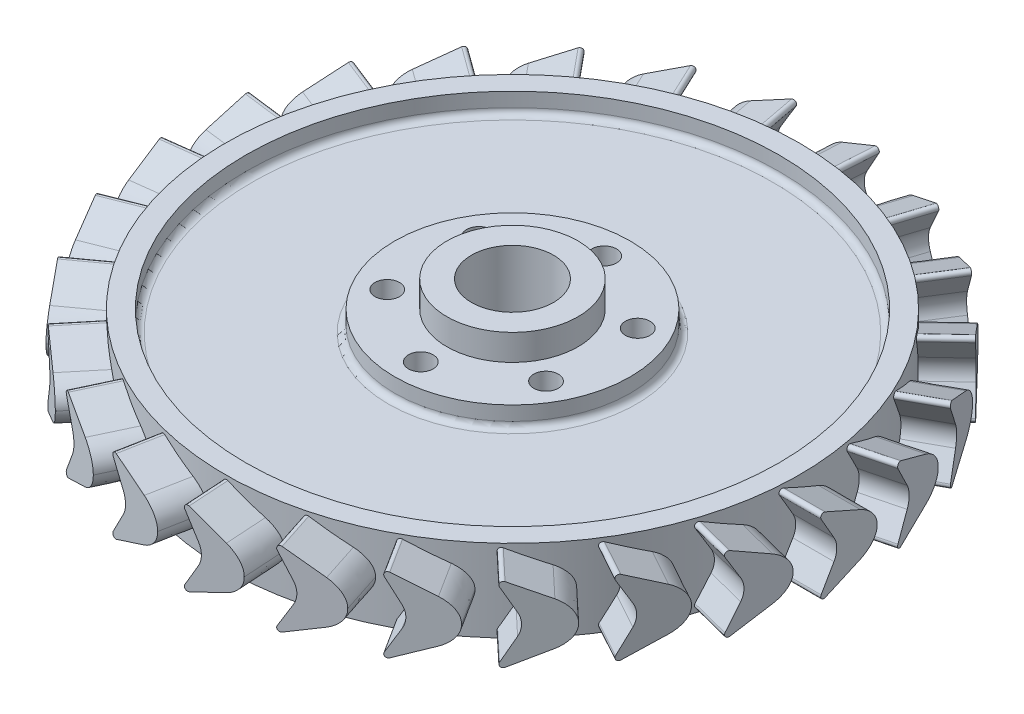
SolidWorks part; units mm, degrees
ref_plane "Front Plane" through (0, 0, 0) normal (0, 0, 1) x (1, 0, 0)
ref_plane "Top Plane" through (0, 0, 0) normal (0, 1, 0) x (1, 0, 0)
ref_plane "Right Plane" through (0, 0, 0) normal (1, 0, 0) x (0, 0, -1)
sketch "Sketch1" plane through (0, 0, 0) normal (0, 0, 1) x (1, 0, 0)
  line L0 (0, 0) -> (0, 10)
  line L3 (32.5, 7.5) -> (32.5, 10)
  line L4 (32.5, 10) -> (35, 10)
  line L5 (35, 10) -> (35, 0)
  line L6 (35, 0) -> (32.5, 0)
  line L7 (32.5, 0) -> (32.5, 2.5)
  line L9 (14.35, 0) -> (0, 0)
  line L10 (0, 5) -> (35, 5) construction
  line L11 (32.5, 7.5) -> (14.35, 7.5)
  line L12 (14.35, 7.5) -> (14.35, 10)
  line L13 (14.35, 0) -> (14.35, 2.5)
  line L14 (14.35, 2.5) -> (32.5, 2.5)
  line L15 (14.35, 10) -> (8, 10)
  line L16 (8, 10) -> (8, 13.175)
  line L17 (8, 13.175) -> (0, 13.175)
  line L18 (0, 13.175) -> (0, 10)
  dimension "D1" = 35
  dimension "D2" = 10
  dimension "D3" = 2.5
  dimension "D4" = 5
  dimension "D6" = 14.35
  dimension "D5" = 10
  dimension "D7" = 3.175
  dimension "D8" = 8
revolve "Main Body" add sketch "Sketch1" angle 360 about L0
fillet "Hub Fillets" radius 0.762 4 edges at (0, 7.5, -14.35) (0, 7.5, -32.5) (0, 2.5, -14.35) (0, 2.5, -32.5)
ref_plane "Blade Drawing Plane" through (35, 0, 0) normal (1, 0, 0) x (0, 0, -1)
sketch "Sketch3" plane through (0, 0, 0) normal (0, -1, 0) x (-1, 0, 0)
  point P0 (0, 11.175)
  dimension "D1" = 11.175
hole_wizard "Ø4.0mm Dowel Hole1" positions "Sketch3" profile "Sketch4" hole size "Ø4.0" standard "ANSI Metric" end condition through all
sketch "Sketch4" plane through (0, 0, -11.175) normal (1, 0, 0) x (0, 0, -1)
  line L0 (0, 0) -> (0, 13.175)
  line L1 (0, 13.175) -> (1.5, 13.175)
  line L2 (1.5, 13.175) -> (1.5, 0)
  line L5 (1.5, 0) -> (0, 0)
  line L11 (0, -6.35) -> (0, 107.95) construction
  dimension "Thru Hole Dia." = 3
  dimension "Thru Hole Depth" = 13.175
pattern_circular "CirPattern1" count 6 over 360 about axis through (0, 0, 0) along (0, -1, 0) of "Ø4.0mm Dowel Hole1"
sketch "Sketch5" plane through (0, 13.175, 0) normal (0, 1, 0) x (1, 0, 0)
  point P0 (0, 0)
hole_wizard "Ø10.0mm Dowel Hole1" positions "Sketch5" profile "Sketch6" hole size "Ø10.0" standard "ANSI Metric" end condition through all
sketch "Sketch6" plane through (0, 13.175, 0) normal (1, 0, 0) x (0, 0, 1)
  line L0 (0, 0) -> (0, 13.175)
  line L1 (0, 13.175) -> (5, 13.175)
  line L2 (5, 13.175) -> (5, 0)
  line L5 (5, 0) -> (0, 0)
  line L11 (0, -6.35) -> (0, 107.95) construction
  dimension "Thru Hole Dia." = 10
  dimension "Thru Hole Depth" = 13.175
sketch "Sketch11" plane through (35, 0, 0) normal (1, 0, 0) x (0, 0, -1)
  line L0 (0, 630) -> (840, 630)
  line L1 (840, 630) -> (840, 0)
  line L2 (840, 0) -> (0, 0)
  line L3 (0, 0) -> (0, 630)
  line L4 (0, 630) -> (840, 630)
  line L5 (840, 630) -> (840, 0)
  line L6 (840, 0) -> (0, 0)
  line L7 (0, 0) -> (0, 630)
  line L8 (618.7249, 408.0901) -> (620.1519, 404.8008)
  line L9 (620.1519, 404.8008) -> (621.579, 401.5114)
  line L10 (621.579, 401.5114) -> (623.006, 398.2221)
  line L11 (623.006, 398.2221) -> (624.433, 394.9328)
  line L12 (624.433, 394.9328) -> (625.86, 391.6435)
  line L13 (625.86, 391.6435) -> (627.287, 388.3542)
  line L14 (627.287, 388.3542) -> (628.7141, 385.0649)
  line L15 (628.7141, 385.0649) -> (630.1411, 381.7756)
  line L16 (630.1411, 381.7756) -> (631.5681, 378.4863)
  line L17 (631.5681, 378.4863) -> (632.9951, 375.197)
  line L18 (632.9951, 375.197) -> (634.4221, 371.9077)
  line L19 (634.4221, 371.9077) -> (635.8492, 368.6183)
  line L20 (635.8492, 368.6183) -> (637.2762, 365.329)
  line L21 (637.2762, 365.329) -> (638.7032, 362.0397)
  line L22 (638.7032, 362.0397) -> (640.1302, 358.7504)
  line L23 (640.1302, 358.7504) -> (641.5573, 355.4611)
  line L24 (641.5573, 355.4611) -> (642.9843, 352.1718)
  line L25 (642.9843, 352.1718) -> (644.4113, 348.8825)
  line L26 (644.4113, 348.8825) -> (645.8383, 345.5932)
  line L27 (645.8383, 345.5932) -> (647.2653, 342.3039)
  line L28 (647.2653, 342.3039) -> (648.6924, 339.0146)
  line L29 (648.6924, 339.0146) -> (650.1194, 335.7252)
  line L30 (650.1194, 335.7252) -> (651.5464, 332.4359)
  line L31 (651.5464, 332.4359) -> (652.9734, 329.1466)
  line L32 (652.9734, 329.1466) -> (654.4005, 325.8573)
  line L33 (654.4005, 325.8573) -> (655.8275, 322.568)
  line L34 (655.8275, 322.568) -> (657.2545, 319.2787)
  line L35 (657.2545, 319.2787) -> (658.6815, 315.9894)
  line L36 (658.6815, 315.9894) -> (660.1085, 312.7001)
  line L37 (660.1085, 312.7001) -> (661.5355, 309.4107)
  line L38 (661.5355, 309.4107) -> (662.9626, 306.1214)
  line L39 (662.9626, 306.1214) -> (664.3896, 302.8321)
  line L40 (664.3896, 302.8321) -> (665.8167, 299.5428)
  line L41 (665.8167, 299.5428) -> (667.2437, 296.2535)
  line L42 (667.2437, 296.2535) -> (668.6707, 292.9642)
  line L43 (668.6707, 292.9642) -> (670.0977, 289.6749)
  line L44 (670.0977, 289.6749) -> (671.5247, 286.3856)
  line L45 (671.5247, 286.3856) -> (672.9517, 283.0963)
  line L46 (672.9517, 283.0963) -> (674.3787, 279.8069)
  line L47 (674.3787, 279.8069) -> (675.8057, 276.5176)
  line L48 (675.8057, 276.5176) -> (677.2328, 273.2283)
  line L49 (677.2328, 273.2283) -> (678.6598, 269.939)
  line L50 (678.6598, 269.939) -> (680.0869, 266.6497)
  line L51 (680.0869, 266.6497) -> (681.5139, 263.3604)
  line L52 (681.5139, 263.3604) -> (682.9409, 260.0711)
  line L53 (682.9409, 260.0711) -> (684.3679, 256.7818)
  line L54 (684.3679, 256.7818) -> (685.7949, 253.4925)
  line L55 (685.7949, 253.4925) -> (687.2219, 250.2032)
  line L56 (687.2219, 250.2032) -> (688.6489, 246.9138)
  line L57 (688.6489, 246.9138) -> (690.076, 243.6245)
  line L58 (690.076, 243.6245) -> (691.503, 240.3352)
  line L59 (691.503, 240.3352) -> (692.93, 237.0459)
  line L60 (692.93, 237.0459) -> (694.3571, 233.7566)
  line L61 (694.3571, 233.7566) -> (695.7841, 230.4673)
  line L62 (695.7841, 230.4673) -> (697.2111, 227.178)
  line L63 (697.2111, 227.178) -> (698.6381, 223.8887)
  line L64 (698.6381, 223.8887) -> (700.0651, 220.5993)
  line L65 (700.0651, 220.5993) -> (701.4921, 217.31)
  line L66 (701.4921, 217.31) -> (702.9191, 214.0207)
  line L67 (702.9191, 214.0207) -> (704.3462, 210.7314)
  line L68 (704.3462, 210.7314) -> (705.7732, 207.4421)
  line L69 (705.7732, 207.4421) -> (707.2002, 204.1528)
  line L70 (707.2002, 204.1528) -> (708.6273, 200.8635)
  line L71 (708.6273, 200.8635) -> (710.0543, 197.5742)
  line L72 (710.0543, 197.5742) -> (711.4813, 194.2849)
  line L73 (711.4813, 194.2849) -> (712.9083, 190.9955)
  line L74 (712.9083, 190.9955) -> (714.3353, 187.7062)
  line L75 (714.3353, 187.7062) -> (715.7623, 184.4169)
  line L76 (715.7623, 184.4169) -> (717.1893, 181.1276)
  line L77 (717.1893, 181.1276) -> (718.6164, 177.8383)
  line L78 (718.6164, 177.8383) -> (720.0434, 174.549)
  line L79 (720.0434, 174.549) -> (721.4705, 171.2597)
  line L80 (721.4705, 171.2597) -> (722.8975, 167.9704)
  line L81 (722.8975, 167.9704) -> (724.3245, 164.6811)
  line L82 (724.3245, 164.6811) -> (725.7515, 161.3918)
  line L83 (725.7515, 161.3918) -> (727.1785, 158.1024)
  line L84 (727.1785, 158.1024) -> (728.6055, 154.8131)
  line L85 (728.6055, 154.8131) -> (730.0325, 151.5238)
  line L86 (730.0325, 151.5238) -> (731.4596, 148.2345)
  line L87 (731.4596, 148.2345) -> (732.8866, 144.9452)
  line L88 (732.8866, 144.9452) -> (734.3136, 141.6559)
  line L89 (734.3136, 141.6559) -> (735.7407, 138.3666)
  line L90 (735.7407, 138.3666) -> (737.1677, 135.0773)
  line L91 (737.1677, 135.0773) -> (738.5947, 131.788)
  line L92 (738.5947, 131.788) -> (740.0217, 128.4987)
  line L93 (740.0217, 128.4987) -> (741.4487, 125.2093)
  line L94 (741.4487, 125.2093) -> (742.8757, 121.92)
  line L95 (742.8757, 121.92) -> (744.3027, 118.6307)
  line L96 (744.3027, 118.6307) -> (745.7298, 115.3414)
  line L97 (745.7298, 115.3414) -> (747.1568, 112.0521)
  line L98 (747.1568, 112.0521) -> (748.5838, 108.7628)
  line L99 (748.5838, 108.7628) -> (750.0109, 105.4734)
  line L100 (750.0109, 105.4734) -> (751.4379, 102.1841)
  line L101 (751.4379, 102.1841) -> (752.8649, 98.8948)
  line L102 (752.8649, 98.8948) -> (754.2919, 95.6055)
  line L103 (754.2919, 95.6055) -> (755.719, 92.3162)
  line L104 (755.719, 92.3162) -> (757.1459, 89.0269)
  line L105 (757.1459, 89.0269) -> (758.5729, 85.7376)
  line L106 (758.5729, 85.7376) -> (760, 82.4483)
  line L107 (109, 82.4483) -> (110.427, 85.7376)
  line L108 (110.427, 85.7376) -> (111.854, 89.0269)
  line L109 (111.854, 89.0269) -> (113.2811, 92.3162)
  line L110 (113.2811, 92.3162) -> (114.7081, 95.6055)
  line L111 (114.7081, 95.6055) -> (116.1351, 98.8948)
  line L112 (116.1351, 98.8948) -> (117.5621, 102.1841)
  line L113 (117.5621, 102.1841) -> (118.9891, 105.4734)
  line L114 (118.9891, 105.4734) -> (120.4162, 108.7628)
  line L115 (120.4162, 108.7628) -> (121.8432, 112.0521)
  line L116 (121.8432, 112.0521) -> (123.2702, 115.3414)
  line L117 (123.2702, 115.3414) -> (124.6972, 118.6307)
  line L118 (124.6972, 118.6307) -> (126.1243, 121.92)
  line L119 (126.1243, 121.92) -> (127.5513, 125.2093)
  line L120 (127.5513, 125.2093) -> (128.9783, 128.4987)
  line L121 (128.9783, 128.4987) -> (130.4053, 131.788)
  line L122 (130.4053, 131.788) -> (131.8323, 135.0773)
  line L123 (131.8323, 135.0773) -> (133.2594, 138.3666)
  line L124 (133.2594, 138.3666) -> (134.6864, 141.6559)
  line L125 (134.6864, 141.6559) -> (136.1134, 144.9452)
  line L126 (136.1134, 144.9452) -> (137.5404, 148.2345)
  line L127 (137.5404, 148.2345) -> (138.9674, 151.5238)
  line L128 (138.9674, 151.5238) -> (140.3945, 154.8131)
  line L129 (140.3945, 154.8131) -> (141.8215, 158.1024)
  line L130 (141.8215, 158.1024) -> (143.2485, 161.3918)
  line L131 (143.2485, 161.3918) -> (144.6755, 164.6811)
  line L132 (144.6755, 164.6811) -> (146.1025, 167.9704)
  line L133 (146.1025, 167.9704) -> (147.5296, 171.2597)
  line L134 (147.5296, 171.2597) -> (148.9566, 174.549)
  line L135 (148.9566, 174.549) -> (150.3836, 177.8383)
  line L136 (150.3836, 177.8383) -> (151.8106, 181.1276)
  line L137 (151.8106, 181.1276) -> (153.2376, 184.4169)
  line L138 (153.2376, 184.4169) -> (154.6647, 187.7062)
  line L139 (154.6647, 187.7062) -> (156.0917, 190.9955)
  line L140 (156.0917, 190.9955) -> (157.5187, 194.2849)
  line L141 (157.5187, 194.2849) -> (158.9457, 197.5742)
  line L142 (158.9457, 197.5742) -> (160.3728, 200.8635)
  line L143 (160.3728, 200.8635) -> (161.7998, 204.1528)
  line L144 (161.7998, 204.1528) -> (163.2268, 207.4421)
  line L145 (163.2268, 207.4421) -> (164.6538, 210.7314)
  line L146 (164.6538, 210.7314) -> (166.0808, 214.0207)
  line L147 (166.0808, 214.0207) -> (167.5079, 217.31)
  line L148 (167.5079, 217.31) -> (168.9349, 220.5993)
  line L149 (168.9349, 220.5993) -> (170.3619, 223.8887)
  line L150 (170.3619, 223.8887) -> (171.7889, 227.178)
  line L151 (171.7889, 227.178) -> (173.2159, 230.4673)
  line L152 (173.2159, 230.4673) -> (174.643, 233.7566)
  line L153 (174.643, 233.7566) -> (176.07, 237.0459)
  line L154 (176.07, 237.0459) -> (177.497, 240.3352)
  line L155 (177.497, 240.3352) -> (178.924, 243.6245)
  line L156 (178.924, 243.6245) -> (180.351, 246.9138)
  line L157 (180.351, 246.9138) -> (181.7781, 250.2032)
  line L158 (181.7781, 250.2032) -> (183.2051, 253.4925)
  line L159 (183.2051, 253.4925) -> (184.6321, 256.7818)
  line L160 (184.6321, 256.7818) -> (186.0591, 260.0711)
  line L161 (186.0591, 260.0711) -> (187.4861, 263.3604)
  line L162 (187.4861, 263.3604) -> (188.9132, 266.6497)
  line L163 (188.9132, 266.6497) -> (190.3402, 269.939)
  line L164 (190.3402, 269.939) -> (191.7672, 273.2283)
  line L165 (191.7672, 273.2283) -> (193.1942, 276.5176)
  line L166 (193.1942, 276.5176) -> (194.6213, 279.8069)
  line L167 (194.6213, 279.8069) -> (196.0483, 283.0963)
  line L168 (196.0483, 283.0963) -> (197.4753, 286.3856)
  line L169 (197.4753, 286.3856) -> (198.9023, 289.6749)
  line L170 (198.9023, 289.6749) -> (200.3293, 292.9642)
  line L171 (200.3293, 292.9642) -> (201.7564, 296.2535)
  line L172 (201.7564, 296.2535) -> (203.1834, 299.5428)
  line L173 (203.1834, 299.5428) -> (204.6104, 302.8321)
  line L174 (204.6104, 302.8321) -> (206.0374, 306.1214)
  line L175 (206.0374, 306.1214) -> (207.4644, 309.4107)
  line L176 (207.4644, 309.4107) -> (208.8915, 312.7001)
  line L177 (208.8915, 312.7001) -> (210.3185, 315.9894)
  line L178 (210.3185, 315.9894) -> (211.7455, 319.2787)
  line L179 (211.7455, 319.2787) -> (213.1725, 322.568)
  line L180 (213.1725, 322.568) -> (214.5995, 325.8573)
  line L181 (214.5995, 325.8573) -> (216.0266, 329.1466)
  line L182 (216.0266, 329.1466) -> (217.4536, 332.4359)
  line L183 (217.4536, 332.4359) -> (218.8806, 335.7252)
  line L184 (218.8806, 335.7252) -> (220.3076, 339.0146)
  line L185 (220.3076, 339.0146) -> (221.7346, 342.3039)
  line L186 (221.7346, 342.3039) -> (223.1617, 345.5932)
  line L187 (223.1617, 345.5932) -> (224.5887, 348.8825)
  line L188 (224.5887, 348.8825) -> (226.0157, 352.1718)
  line L189 (226.0157, 352.1718) -> (227.4427, 355.4611)
  line L190 (227.4427, 355.4611) -> (228.8698, 358.7504)
  line L191 (228.8698, 358.7504) -> (230.2968, 362.0397)
  line L192 (230.2968, 362.0397) -> (231.7238, 365.329)
  line L193 (231.7238, 365.329) -> (233.1508, 368.6183)
  line L194 (233.1508, 368.6183) -> (234.5778, 371.9077)
  line L195 (234.5778, 371.9077) -> (236.0049, 375.197)
  line L196 (236.0049, 375.197) -> (237.4319, 378.4863)
  line L197 (237.4319, 378.4863) -> (238.8589, 381.7756)
  line L198 (238.8589, 381.7756) -> (240.2859, 385.0649)
  line L199 (240.2859, 385.0649) -> (241.713, 388.3542)
  line L200 (241.713, 388.3542) -> (243.14, 391.6435)
  line L201 (243.14, 391.6435) -> (244.567, 394.9328)
  line L202 (244.567, 394.9328) -> (245.994, 398.2221)
  line L203 (245.994, 398.2221) -> (247.421, 401.5114)
  line L204 (247.421, 401.5114) -> (248.8481, 404.8008)
  line L205 (248.8481, 404.8008) -> (250.2751, 408.0901)
  line L206 (618.7249, 408.0901) -> (617.3053, 411.3354)
  line L207 (617.3053, 411.3354) -> (615.8767, 414.5479)
  line L208 (615.8767, 414.5479) -> (614.4391, 417.7274)
  line L209 (614.4391, 417.7274) -> (612.9924, 420.8739)
  line L210 (612.9924, 420.8739) -> (611.5368, 423.9875)
  line L211 (611.5368, 423.9875) -> (610.0722, 427.0681)
  line L212 (610.0722, 427.0681) -> (608.5986, 430.1158)
  line L213 (608.5986, 430.1158) -> (607.1159, 433.1306)
  line L214 (607.1159, 433.1306) -> (605.6243, 436.1124)
  line L215 (605.6243, 436.1124) -> (604.1236, 439.0612)
  line L216 (604.1236, 439.0612) -> (602.614, 441.9771)
  line L217 (602.614, 441.9771) -> (601.0953, 444.86)
  line L218 (601.0953, 444.86) -> (599.5676, 447.71)
  line L219 (599.5676, 447.71) -> (598.0309, 450.5271)
  line L220 (598.0309, 450.5271) -> (596.4852, 453.3112)
  line L221 (596.4852, 453.3112) -> (594.9305, 456.0623)
  line L222 (594.9305, 456.0623) -> (593.3669, 458.7806)
  line L223 (593.3669, 458.7806) -> (591.7941, 461.4658)
  line L224 (591.7941, 461.4658) -> (590.2125, 464.1181)
  line L225 (590.2125, 464.1181) -> (588.6218, 466.7375)
  line L226 (588.6218, 466.7375) -> (587.022, 469.3239)
  line L227 (587.022, 469.3239) -> (585.4133, 471.8774)
  line L228 (585.4133, 471.8774) -> (583.7956, 474.3979)
  line L229 (583.7956, 474.3979) -> (582.1689, 476.8855)
  line L230 (582.1689, 476.8855) -> (580.5331, 479.3401)
  line L231 (580.5331, 479.3401) -> (578.8884, 481.7618)
  line L232 (578.8884, 481.7618) -> (577.2347, 484.1505)
  line L233 (577.2347, 484.1505) -> (575.572, 486.5063)
  line L234 (575.572, 486.5063) -> (573.9001, 488.8291)
  line L235 (573.9001, 488.8291) -> (572.2194, 491.119)
  line L236 (572.2194, 491.119) -> (570.5297, 493.376)
  line L237 (570.5297, 493.376) -> (568.8309, 495.6)
  line L238 (568.8309, 495.6) -> (567.1231, 497.791)
  line L239 (567.1231, 497.791) -> (565.4064, 499.9491)
  line L240 (565.4064, 499.9491) -> (563.6805, 502.0742)
  line L241 (563.6805, 502.0742) -> (561.9457, 504.1664)
  line L242 (561.9457, 504.1664) -> (560.202, 506.2257)
  line L243 (560.202, 506.2257) -> (558.4492, 508.252)
  line L244 (558.4492, 508.252) -> (556.6874, 510.2453)
  line L245 (556.6874, 510.2453) -> (554.9166, 512.2057)
  line L246 (554.9166, 512.2057) -> (553.1368, 514.1332)
  line L247 (553.1368, 514.1332) -> (551.348, 516.0277)
  line L248 (551.348, 516.0277) -> (549.5501, 517.8892)
  line L249 (549.5501, 517.8892) -> (547.7433, 519.7179)
  line L250 (547.7433, 519.7179) -> (545.9274, 521.5135)
  line L251 (545.9274, 521.5135) -> (544.1026, 523.2763)
  line L252 (544.1026, 523.2763) -> (542.2687, 525.006)
  line L253 (542.2687, 525.006) -> (540.426, 526.7028)
  line L254 (540.426, 526.7028) -> (538.5741, 528.3667)
  line L255 (538.5741, 528.3667) -> (536.7133, 529.9976)
  line L256 (536.7133, 529.9976) -> (534.8434, 531.5956)
  line L257 (534.8434, 531.5956) -> (532.9645, 533.1607)
  line L258 (532.9645, 533.1607) -> (531.0766, 534.6927)
  line L259 (531.0766, 534.6927) -> (529.1797, 536.1919)
  line L260 (529.1797, 536.1919) -> (527.2739, 537.6581)
  line L261 (527.2739, 537.6581) -> (525.3589, 539.0913)
  line L262 (525.3589, 539.0913) -> (523.4351, 540.4916)
  line L263 (523.4351, 540.4916) -> (521.5022, 541.8589)
  line L264 (521.5022, 541.8589) -> (519.5603, 543.1933)
  line L265 (519.5603, 543.1933) -> (517.6094, 544.4947)
  line L266 (517.6094, 544.4947) -> (515.6494, 545.7633)
  line L267 (515.6494, 545.7633) -> (513.6805, 546.9988)
  line L268 (513.6805, 546.9988) -> (511.7026, 548.2014)
  line L269 (511.7026, 548.2014) -> (509.7157, 549.3711)
  line L270 (509.7157, 549.3711) -> (507.7198, 550.5078)
  line L271 (507.7198, 550.5078) -> (505.7148, 551.6115)
  line L272 (505.7148, 551.6115) -> (503.7009, 552.6823)
  line L273 (503.7009, 552.6823) -> (501.6779, 553.7202)
  line L274 (501.6779, 553.7202) -> (499.646, 554.7251)
  line L275 (499.646, 554.7251) -> (497.605, 555.6971)
  line L276 (497.605, 555.6971) -> (495.5551, 556.6361)
  line L277 (495.5551, 556.6361) -> (493.4961, 557.5422)
  line L278 (493.4961, 557.5422) -> (491.4281, 558.4153)
  line L279 (491.4281, 558.4153) -> (489.3511, 559.2554)
  line L280 (489.3511, 559.2554) -> (487.2651, 560.0627)
  line L281 (487.2651, 560.0627) -> (485.1702, 560.837)
  line L282 (485.1702, 560.837) -> (483.0661, 561.5783)
  line L283 (483.0661, 561.5783) -> (480.9532, 562.2867)
  line L284 (480.9532, 562.2867) -> (478.8311, 562.9621)
  line L285 (478.8311, 562.9621) -> (476.7002, 563.6046)
  line L286 (476.7002, 563.6046) -> (474.5601, 564.2141)
  line L287 (474.5601, 564.2141) -> (472.4111, 564.7907)
  line L288 (472.4111, 564.7907) -> (470.2531, 565.3344)
  line L289 (470.2531, 565.3344) -> (468.0861, 565.8451)
  line L290 (468.0861, 565.8451) -> (465.91, 566.3228)
  line L291 (465.91, 566.3228) -> (463.725, 566.7676)
  line L292 (463.725, 566.7676) -> (461.5309, 567.1795)
  line L293 (461.5309, 567.1795) -> (459.3279, 567.5584)
  line L294 (459.3279, 567.5584) -> (457.1158, 567.9043)
  line L295 (457.1158, 567.9043) -> (454.8948, 568.2173)
  line L296 (454.8948, 568.2173) -> (452.6647, 568.4974)
  line L297 (452.6647, 568.4974) -> (450.4256, 568.7445)
  line L298 (450.4256, 568.7445) -> (448.1776, 568.9586)
  line L299 (448.1776, 568.9586) -> (445.9205, 569.1399)
  line L300 (445.9205, 569.1399) -> (443.6544, 569.2881)
  line L301 (443.6544, 569.2881) -> (441.3793, 569.4035)
  line L302 (441.3793, 569.4035) -> (439.0952, 569.4858)
  line L303 (439.0952, 569.4858) -> (436.8021, 569.5352)
  line L304 (436.8021, 569.5352) -> (434.5, 569.5517)
  line L305 (250.2751, 408.0901) -> (251.6947, 411.3354)
  line L306 (251.6947, 411.3354) -> (253.1233, 414.5479)
  line L307 (253.1233, 414.5479) -> (254.5609, 417.7274)
  line L308 (254.5609, 417.7274) -> (256.0075, 420.8739)
  line L309 (256.0075, 420.8739) -> (257.4632, 423.9875)
  line L310 (257.4632, 423.9875) -> (258.9278, 427.0681)
  line L311 (258.9278, 427.0681) -> (260.4015, 430.1158)
  line L312 (260.4015, 430.1158) -> (261.8841, 433.1306)
  line L313 (261.8841, 433.1306) -> (263.3758, 436.1124)
  line L314 (263.3758, 436.1124) -> (264.8764, 439.0612)
  line L315 (264.8764, 439.0612) -> (266.3861, 441.9771)
  line L316 (266.3861, 441.9771) -> (267.9047, 444.86)
  line L317 (267.9047, 444.86) -> (269.4324, 447.71)
  line L318 (269.4324, 447.71) -> (270.9691, 450.5271)
  line L319 (270.9691, 450.5271) -> (272.5148, 453.3112)
  line L320 (272.5148, 453.3112) -> (274.0695, 456.0623)
  line L321 (274.0695, 456.0623) -> (275.6331, 458.7806)
  line L322 (275.6331, 458.7806) -> (277.2058, 461.4658)
  line L323 (277.2058, 461.4658) -> (278.7875, 464.1181)
  line L324 (278.7875, 464.1181) -> (280.3782, 466.7375)
  line L325 (280.3782, 466.7375) -> (281.978, 469.3239)
  line L326 (281.978, 469.3239) -> (283.5867, 471.8774)
  line L327 (283.5867, 471.8774) -> (285.2044, 474.3979)
  line L328 (285.2044, 474.3979) -> (286.8311, 476.8855)
  line L329 (286.8311, 476.8855) -> (288.4669, 479.3401)
  line L330 (288.4669, 479.3401) -> (290.1116, 481.7618)
  line L331 (290.1116, 481.7618) -> (291.7653, 484.1505)
  line L332 (291.7653, 484.1505) -> (293.4281, 486.5063)
  line L333 (293.4281, 486.5063) -> (295.0998, 488.8291)
  line L334 (295.0998, 488.8291) -> (296.7806, 491.119)
  line L335 (296.7806, 491.119) -> (298.4703, 493.376)
  line L336 (298.4703, 493.376) -> (300.1691, 495.6)
  line L337 (300.1691, 495.6) -> (301.8769, 497.791)
  line L338 (301.8769, 497.791) -> (303.5937, 499.9491)
  line L339 (303.5937, 499.9491) -> (305.3195, 502.0742)
  line L340 (305.3195, 502.0742) -> (307.0542, 504.1664)
  line L341 (307.0542, 504.1664) -> (308.798, 506.2257)
  line L342 (308.798, 506.2257) -> (310.5508, 508.252)
  line L343 (310.5508, 508.252) -> (312.3126, 510.2453)
  line L344 (312.3126, 510.2453) -> (314.0834, 512.2057)
  line L345 (314.0834, 512.2057) -> (315.8633, 514.1332)
  line L346 (315.8633, 514.1332) -> (317.6521, 516.0277)
  line L347 (317.6521, 516.0277) -> (319.4499, 517.8892)
  line L348 (319.4499, 517.8892) -> (321.2567, 519.7179)
  line L349 (321.2567, 519.7179) -> (323.0725, 521.5135)
  line L350 (323.0725, 521.5135) -> (324.8974, 523.2763)
  line L351 (324.8974, 523.2763) -> (326.7312, 525.006)
  line L352 (326.7312, 525.006) -> (328.5741, 526.7028)
  line L353 (328.5741, 526.7028) -> (330.4259, 528.3667)
  line L354 (330.4259, 528.3667) -> (332.2868, 529.9976)
  line L355 (332.2868, 529.9976) -> (334.1566, 531.5956)
  line L356 (334.1566, 531.5956) -> (336.0355, 533.1607)
  line L357 (336.0355, 533.1607) -> (337.9234, 534.6927)
  line L358 (337.9234, 534.6927) -> (339.8203, 536.1919)
  line L359 (339.8203, 536.1919) -> (341.7261, 537.6581)
  line L360 (341.7261, 537.6581) -> (343.641, 539.0913)
  line L361 (343.641, 539.0913) -> (345.5649, 540.4916)
  line L362 (345.5649, 540.4916) -> (347.4978, 541.8589)
  line L363 (347.4978, 541.8589) -> (349.4397, 543.1933)
  line L364 (349.4397, 543.1933) -> (351.3906, 544.4947)
  line L365 (351.3906, 544.4947) -> (353.3506, 545.7633)
  line L366 (353.3506, 545.7633) -> (355.3195, 546.9988)
  line L367 (355.3195, 546.9988) -> (357.2974, 548.2014)
  line L368 (357.2974, 548.2014) -> (359.2843, 549.3711)
  line L369 (359.2843, 549.3711) -> (361.2803, 550.5078)
  line L370 (361.2803, 550.5078) -> (363.2852, 551.6115)
  line L371 (363.2852, 551.6115) -> (365.2992, 552.6823)
  line L372 (365.2992, 552.6823) -> (367.3221, 553.7202)
  line L373 (367.3221, 553.7202) -> (369.354, 554.7251)
  line L374 (369.354, 554.7251) -> (371.395, 555.6971)
  line L375 (371.395, 555.6971) -> (373.445, 556.6361)
  line L376 (373.445, 556.6361) -> (375.5039, 557.5422)
  line L377 (375.5039, 557.5422) -> (377.5719, 558.4153)
  line L378 (377.5719, 558.4153) -> (379.6489, 559.2554)
  line L379 (379.6489, 559.2554) -> (381.7349, 560.0627)
  line L380 (381.7349, 560.0627) -> (383.8299, 560.837)
  line L381 (383.8299, 560.837) -> (385.9338, 561.5783)
  line L382 (385.9338, 561.5783) -> (388.0468, 562.2867)
  line L383 (388.0468, 562.2867) -> (390.1689, 562.9621)
  line L384 (390.1689, 562.9621) -> (392.2999, 563.6046)
  line L385 (392.2999, 563.6046) -> (394.4399, 564.2141)
  line L386 (394.4399, 564.2141) -> (396.5889, 564.7907)
  line L387 (396.5889, 564.7907) -> (398.7469, 565.3344)
  line L388 (398.7469, 565.3344) -> (400.914, 565.8451)
  line L389 (400.914, 565.8451) -> (403.09, 566.3228)
  line L390 (403.09, 566.3228) -> (405.275, 566.7676)
  line L391 (405.275, 566.7676) -> (407.4691, 567.1795)
  line L392 (407.4691, 567.1795) -> (409.6721, 567.5584)
  line L393 (409.6721, 567.5584) -> (411.8842, 567.9043)
  line L394 (411.8842, 567.9043) -> (414.1053, 568.2173)
  line L395 (414.1053, 568.2173) -> (416.3353, 568.4974)
  line L396 (416.3353, 568.4974) -> (418.5744, 568.7445)
  line L397 (418.5744, 568.7445) -> (420.8224, 568.9586)
  line L398 (420.8224, 568.9586) -> (423.0795, 569.1399)
  line L399 (423.0795, 569.1399) -> (425.3456, 569.2881)
  line L400 (425.3456, 569.2881) -> (427.6207, 569.4035)
  line L401 (427.6207, 569.4035) -> (429.9048, 569.4858)
  line L402 (429.9048, 569.4858) -> (432.1979, 569.5352)
  line L403 (432.1979, 569.5352) -> (434.5, 569.5517)
  line L404 (514.7324, 222.7281) -> (517.2099, 221.3111)
  line L405 (517.2099, 221.3111) -> (519.6874, 219.8941)
  line L406 (519.6874, 219.8941) -> (522.1648, 218.4772)
  line L407 (522.1648, 218.4772) -> (524.6423, 217.0602)
  line L408 (524.6423, 217.0602) -> (527.1197, 215.6432)
  line L409 (527.1197, 215.6432) -> (529.5972, 214.2263)
  line L410 (529.5972, 214.2263) -> (532.0746, 212.8093)
  line L411 (532.0746, 212.8093) -> (534.5521, 211.3923)
  line L412 (534.5521, 211.3923) -> (537.0295, 209.9754)
  line L413 (537.0295, 209.9754) -> (539.507, 208.5584)
  line L414 (539.507, 208.5584) -> (541.9844, 207.1414)
  line L415 (541.9844, 207.1414) -> (544.4619, 205.7245)
  line L416 (544.4619, 205.7245) -> (546.9393, 204.3075)
  line L417 (546.9393, 204.3075) -> (549.4167, 202.8905)
  line L418 (549.4167, 202.8905) -> (551.8942, 201.4736)
  line L419 (551.8942, 201.4736) -> (554.3716, 200.0566)
  line L420 (554.3716, 200.0566) -> (556.8491, 198.6396)
  line L421 (556.8491, 198.6396) -> (559.3265, 197.2227)
  line L422 (559.3265, 197.2227) -> (561.804, 195.8057)
  line L423 (561.804, 195.8057) -> (564.2814, 194.3887)
  line L424 (564.2814, 194.3887) -> (566.7589, 192.9718)
  line L425 (566.7589, 192.9718) -> (569.2363, 191.5548)
  line L426 (569.2363, 191.5548) -> (571.7138, 190.1378)
  line L427 (571.7138, 190.1378) -> (574.1913, 188.7209)
  line L428 (574.1913, 188.7209) -> (576.6687, 187.3039)
  line L429 (576.6687, 187.3039) -> (579.1461, 185.8869)
  line L430 (579.1461, 185.8869) -> (581.6236, 184.4699)
  line L431 (581.6236, 184.4699) -> (584.1011, 183.053)
  line L432 (584.1011, 183.053) -> (586.5785, 181.636)
  line L433 (586.5785, 181.636) -> (589.056, 180.2191)
  line L434 (589.056, 180.2191) -> (591.5334, 178.8021)
  line L435 (591.5334, 178.8021) -> (594.0109, 177.3851)
  line L436 (594.0109, 177.3851) -> (596.4883, 175.9681)
  line L437 (596.4883, 175.9681) -> (598.9658, 174.5512)
  line L438 (598.9658, 174.5512) -> (601.4432, 173.1342)
  line L439 (601.4432, 173.1342) -> (603.9207, 171.7173)
  line L440 (603.9207, 171.7173) -> (606.3981, 170.3003)
  line L441 (606.3981, 170.3003) -> (608.8755, 168.8833)
  line L442 (608.8755, 168.8833) -> (611.353, 167.4663)
  line L443 (611.353, 167.4663) -> (613.8304, 166.0494)
  line L444 (613.8304, 166.0494) -> (616.3079, 164.6324)
  line L445 (616.3079, 164.6324) -> (618.7853, 163.2154)
  line L446 (618.7853, 163.2154) -> (621.2628, 161.7985)
  line L447 (621.2628, 161.7985) -> (623.7403, 160.3815)
  line L448 (623.7403, 160.3815) -> (626.2177, 158.9645)
  line L449 (626.2177, 158.9645) -> (628.6952, 157.5476)
  line L450 (628.6952, 157.5476) -> (631.1726, 156.1306)
  line L451 (631.1726, 156.1306) -> (633.65, 154.7136)
  line L452 (633.65, 154.7136) -> (636.1275, 153.2967)
  line L453 (636.1275, 153.2967) -> (638.6049, 151.8797)
  line L454 (638.6049, 151.8797) -> (641.0825, 150.4627)
  line L455 (641.0825, 150.4627) -> (643.5599, 149.0458)
  line L456 (643.5599, 149.0458) -> (646.0373, 147.6288)
  line L457 (646.0373, 147.6288) -> (648.5148, 146.2118)
  line L458 (648.5148, 146.2118) -> (650.9922, 144.7949)
  line L459 (650.9922, 144.7949) -> (653.4696, 143.3779)
  line L460 (653.4696, 143.3779) -> (655.9471, 141.9609)
  line L461 (655.9471, 141.9609) -> (658.4246, 140.5439)
  line L462 (658.4246, 140.5439) -> (660.902, 139.127)
  line L463 (660.902, 139.127) -> (663.3795, 137.71)
  line L464 (663.3795, 137.71) -> (665.8569, 136.2931)
  line L465 (665.8569, 136.2931) -> (668.3344, 134.8761)
  line L466 (668.3344, 134.8761) -> (670.8118, 133.4591)
  line L467 (670.8118, 133.4591) -> (673.2893, 132.0421)
  line L468 (673.2893, 132.0421) -> (675.7667, 130.6252)
  line L469 (675.7667, 130.6252) -> (678.2441, 129.2082)
  line L470 (678.2441, 129.2082) -> (680.7216, 127.7913)
  line L471 (680.7216, 127.7913) -> (683.199, 126.3743)
  line L472 (683.199, 126.3743) -> (685.6765, 124.9573)
  line L473 (685.6765, 124.9573) -> (688.1539, 123.5403)
  line L474 (688.1539, 123.5403) -> (690.6314, 122.1234)
  line L475 (690.6314, 122.1234) -> (693.1089, 120.7064)
  line L476 (693.1089, 120.7064) -> (695.5863, 119.2895)
  line L477 (695.5863, 119.2895) -> (698.0637, 117.8725)
  line L478 (698.0637, 117.8725) -> (700.5412, 116.4555)
  line L479 (700.5412, 116.4555) -> (703.0186, 115.0385)
  line L480 (703.0186, 115.0385) -> (705.4961, 113.6216)
  line L481 (705.4961, 113.6216) -> (707.9736, 112.2046)
  line L482 (707.9736, 112.2046) -> (710.451, 110.7877)
  line L483 (710.451, 110.7877) -> (712.9285, 109.3707)
  line L484 (712.9285, 109.3707) -> (715.4059, 107.9537)
  line L485 (715.4059, 107.9537) -> (717.8834, 106.5367)
  line L486 (717.8834, 106.5367) -> (720.3608, 105.1198)
  line L487 (720.3608, 105.1198) -> (722.8383, 103.7028)
  line L488 (722.8383, 103.7028) -> (725.3157, 102.2858)
  line L489 (725.3157, 102.2858) -> (727.7932, 100.8689)
  line L490 (727.7932, 100.8689) -> (730.2706, 99.4519)
  line L491 (730.2706, 99.4519) -> (732.748, 98.0349)
  line L492 (732.748, 98.0349) -> (735.2255, 96.618)
  line L493 (735.2255, 96.618) -> (737.7029, 95.201)
  line L494 (737.7029, 95.201) -> (740.1804, 93.7841)
  line L495 (740.1804, 93.7841) -> (742.6579, 92.3671)
  line L496 (742.6579, 92.3671) -> (745.1353, 90.9501)
  line L497 (745.1353, 90.9501) -> (747.6127, 89.5331)
  line L498 (747.6127, 89.5331) -> (750.0902, 88.1161)
  line L499 (750.0902, 88.1161) -> (752.5676, 86.6992)
  line L500 (752.5676, 86.6992) -> (755.045, 85.2822)
  line L501 (755.045, 85.2822) -> (757.5226, 83.8652)
  line L502 (757.5226, 83.8652) -> (760, 82.4483)
  line L503 (354.2675, 222.7281) -> (355.8884, 223.6428)
  line L504 (355.8884, 223.6428) -> (357.5092, 224.5331)
  line L505 (357.5092, 224.5331) -> (359.1301, 225.3995)
  line L506 (359.1301, 225.3995) -> (360.751, 226.2424)
  line L507 (360.751, 226.2424) -> (362.3718, 227.0622)
  line L508 (362.3718, 227.0622) -> (363.9927, 227.8594)
  line L509 (363.9927, 227.8594) -> (365.6136, 228.6342)
  line L510 (365.6136, 228.6342) -> (367.2344, 229.3871)
  line L511 (367.2344, 229.3871) -> (368.8553, 230.1183)
  line L512 (368.8553, 230.1183) -> (370.4761, 230.8282)
  line L513 (370.4761, 230.8282) -> (372.097, 231.5172)
  line L514 (372.097, 231.5172) -> (373.7178, 232.1854)
  line L515 (373.7178, 232.1854) -> (375.3387, 232.8332)
  line L516 (375.3387, 232.8332) -> (376.9596, 233.4608)
  line L517 (376.9596, 233.4608) -> (378.5804, 234.0684)
  line L518 (378.5804, 234.0684) -> (380.2013, 234.6564)
  line L519 (380.2013, 234.6564) -> (381.8221, 235.2249)
  line L520 (381.8221, 235.2249) -> (383.443, 235.7742)
  line L521 (383.443, 235.7742) -> (385.0638, 236.3045)
  line L522 (385.0638, 236.3045) -> (386.6847, 236.8159)
  line L523 (386.6847, 236.8159) -> (388.3056, 237.3087)
  line L524 (388.3056, 237.3087) -> (389.9264, 237.783)
  line L525 (389.9264, 237.783) -> (391.5473, 238.239)
  line L526 (391.5473, 238.239) -> (393.1681, 238.6768)
  line L527 (393.1681, 238.6768) -> (394.789, 239.0966)
  line L528 (394.789, 239.0966) -> (396.4099, 239.4986)
  line L529 (396.4099, 239.4986) -> (398.0307, 239.8829)
  line L530 (398.0307, 239.8829) -> (399.6516, 240.2496)
  line L531 (399.6516, 240.2496) -> (401.2724, 240.5988)
  line L532 (401.2724, 240.5988) -> (402.8933, 240.9307)
  line L533 (402.8933, 240.9307) -> (404.5141, 241.2454)
  line L534 (404.5141, 241.2454) -> (406.135, 241.5429)
  line L535 (406.135, 241.5429) -> (407.7559, 241.8234)
  line L536 (407.7559, 241.8234) -> (409.3767, 242.0869)
  line L537 (409.3767, 242.0869) -> (410.9976, 242.3336)
  line L538 (410.9976, 242.3336) -> (412.6184, 242.5634)
  line L539 (412.6184, 242.5634) -> (414.2393, 242.7766)
  line L540 (414.2393, 242.7766) -> (415.8601, 242.9731)
  line L541 (415.8601, 242.9731) -> (417.481, 243.153)
  line L542 (417.481, 243.153) -> (419.1018, 243.3164)
  line L543 (419.1018, 243.3164) -> (420.7227, 243.4633)
  line L544 (420.7227, 243.4633) -> (422.3436, 243.5938)
  line L545 (422.3436, 243.5938) -> (423.9644, 243.7079)
  line L546 (423.9644, 243.7079) -> (425.5853, 243.8056)
  line L547 (425.5853, 243.8056) -> (427.2061, 243.887)
  line L548 (427.2061, 243.887) -> (428.827, 243.9521)
  line L549 (428.827, 243.9521) -> (430.4478, 244.0009)
  line L550 (430.4478, 244.0009) -> (432.0687, 244.0334)
  line L551 (432.0687, 244.0334) -> (433.6896, 244.0497)
  line L552 (433.6896, 244.0497) -> (435.3104, 244.0497)
  line L553 (435.3104, 244.0497) -> (436.9313, 244.0334)
  line L554 (436.9313, 244.0334) -> (438.5521, 244.0009)
  line L555 (438.5521, 244.0009) -> (440.173, 243.9521)
  line L556 (440.173, 243.9521) -> (441.7939, 243.887)
  line L557 (441.7939, 243.887) -> (443.4147, 243.8056)
  line L558 (443.4147, 243.8056) -> (445.0356, 243.7079)
  line L559 (445.0356, 243.7079) -> (446.6564, 243.5938)
  line L560 (446.6564, 243.5938) -> (448.2773, 243.4633)
  line L561 (448.2773, 243.4633) -> (449.8981, 243.3164)
  line L562 (449.8981, 243.3164) -> (451.519, 243.153)
  line L563 (451.519, 243.153) -> (453.1399, 242.9731)
  line L564 (453.1399, 242.9731) -> (454.7607, 242.7766)
  line L565 (454.7607, 242.7766) -> (456.3816, 242.5634)
  line L566 (456.3816, 242.5634) -> (458.0024, 242.3336)
  line L567 (458.0024, 242.3336) -> (459.6233, 242.0869)
  line L568 (459.6233, 242.0869) -> (461.2441, 241.8234)
  line L569 (461.2441, 241.8234) -> (462.865, 241.5429)
  line L570 (462.865, 241.5429) -> (464.4859, 241.2454)
  line L571 (464.4859, 241.2454) -> (466.1067, 240.9307)
  line L572 (466.1067, 240.9307) -> (467.7276, 240.5988)
  line L573 (467.7276, 240.5988) -> (469.3484, 240.2496)
  line L574 (469.3484, 240.2496) -> (470.9693, 239.8829)
  line L575 (470.9693, 239.8829) -> (472.5901, 239.4986)
  line L576 (472.5901, 239.4986) -> (474.211, 239.0966)
  line L577 (474.211, 239.0966) -> (475.8319, 238.6768)
  line L578 (475.8319, 238.6768) -> (477.4527, 238.239)
  line L579 (477.4527, 238.239) -> (479.0736, 237.783)
  line L580 (479.0736, 237.783) -> (480.6945, 237.3087)
  line L581 (480.6945, 237.3087) -> (482.3153, 236.8159)
  line L582 (482.3153, 236.8159) -> (483.9362, 236.3045)
  line L583 (483.9362, 236.3045) -> (485.557, 235.7742)
  line L584 (485.557, 235.7742) -> (487.1779, 235.2249)
  line L585 (487.1779, 235.2249) -> (488.7987, 234.6564)
  line L586 (488.7987, 234.6564) -> (490.4196, 234.0684)
  line L587 (490.4196, 234.0684) -> (492.0404, 233.4608)
  line L588 (492.0404, 233.4608) -> (493.6613, 232.8332)
  line L589 (493.6613, 232.8332) -> (495.2822, 232.1854)
  line L590 (495.2822, 232.1854) -> (496.903, 231.5172)
  line L591 (496.903, 231.5172) -> (498.5239, 230.8282)
  line L592 (498.5239, 230.8282) -> (500.1447, 230.1183)
  line L593 (500.1447, 230.1183) -> (501.7656, 229.3871)
  line L594 (501.7656, 229.3871) -> (503.3864, 228.6342)
  line L595 (503.3864, 228.6342) -> (505.0073, 227.8594)
  line L596 (505.0073, 227.8594) -> (506.6282, 227.0622)
  line L597 (506.6282, 227.0622) -> (508.249, 226.2424)
  line L598 (508.249, 226.2424) -> (509.8699, 225.3995)
  line L599 (509.8699, 225.3995) -> (511.4907, 224.5331)
  line L600 (511.4907, 224.5331) -> (513.1116, 223.6428)
  line L601 (513.1116, 223.6428) -> (514.7324, 222.7281)
  line L602 (109, 82.4483) -> (111.4774, 83.8652)
  line L603 (111.4774, 83.8652) -> (113.9549, 85.2822)
  line L604 (113.9549, 85.2822) -> (116.4324, 86.6992)
  line L605 (116.4324, 86.6992) -> (118.9098, 88.1161)
  line L606 (118.9098, 88.1161) -> (121.3873, 89.5331)
  line L607 (121.3873, 89.5331) -> (123.8647, 90.9501)
  line L608 (123.8647, 90.9501) -> (126.3421, 92.3671)
  line L609 (126.3421, 92.3671) -> (128.8196, 93.7841)
  line L610 (128.8196, 93.7841) -> (131.297, 95.201)
  line L611 (131.297, 95.201) -> (133.7745, 96.618)
  line L612 (133.7745, 96.618) -> (136.252, 98.0349)
  line L613 (136.252, 98.0349) -> (138.7294, 99.4519)
  line L614 (138.7294, 99.4519) -> (141.2068, 100.8689)
  line L615 (141.2068, 100.8689) -> (143.6843, 102.2858)
  line L616 (143.6843, 102.2858) -> (146.1617, 103.7028)
  line L617 (146.1617, 103.7028) -> (148.6392, 105.1198)
  line L618 (148.6392, 105.1198) -> (151.1167, 106.5367)
  line L619 (151.1167, 106.5367) -> (153.5941, 107.9537)
  line L620 (153.5941, 107.9537) -> (156.0715, 109.3707)
  line L621 (156.0715, 109.3707) -> (158.549, 110.7877)
  line L622 (158.549, 110.7877) -> (161.0264, 112.2046)
  line L623 (161.0264, 112.2046) -> (163.5039, 113.6216)
  line L624 (163.5039, 113.6216) -> (165.9814, 115.0385)
  line L625 (165.9814, 115.0385) -> (168.4588, 116.4555)
  line L626 (168.4588, 116.4555) -> (170.9362, 117.8725)
  line L627 (170.9362, 117.8725) -> (173.4137, 119.2895)
  line L628 (173.4137, 119.2895) -> (175.8911, 120.7064)
  line L629 (175.8911, 120.7064) -> (178.3686, 122.1234)
  line L630 (178.3686, 122.1234) -> (180.8461, 123.5403)
  line L631 (180.8461, 123.5403) -> (183.3235, 124.9573)
  line L632 (183.3235, 124.9573) -> (185.8009, 126.3743)
  line L633 (185.8009, 126.3743) -> (188.2784, 127.7913)
  line L634 (188.2784, 127.7913) -> (190.7558, 129.2082)
  line L635 (190.7558, 129.2082) -> (193.2333, 130.6252)
  line L636 (193.2333, 130.6252) -> (195.7107, 132.0421)
  line L637 (195.7107, 132.0421) -> (198.1882, 133.4591)
  line L638 (198.1882, 133.4591) -> (200.6656, 134.8761)
  line L639 (200.6656, 134.8761) -> (203.1431, 136.2931)
  line L640 (203.1431, 136.2931) -> (205.6205, 137.71)
  line L641 (205.6205, 137.71) -> (208.098, 139.127)
  line L642 (208.098, 139.127) -> (210.5754, 140.5439)
  line L643 (210.5754, 140.5439) -> (213.0529, 141.9609)
  line L644 (213.0529, 141.9609) -> (215.5303, 143.3779)
  line L645 (215.5303, 143.3779) -> (218.0078, 144.7949)
  line L646 (218.0078, 144.7949) -> (220.4852, 146.2118)
  line L647 (220.4852, 146.2118) -> (222.9627, 147.6288)
  line L648 (222.9627, 147.6288) -> (225.4402, 149.0458)
  line L649 (225.4402, 149.0458) -> (227.9176, 150.4627)
  line L650 (227.9176, 150.4627) -> (230.3951, 151.8797)
  line L651 (230.3951, 151.8797) -> (232.8725, 153.2967)
  line L652 (232.8725, 153.2967) -> (235.3499, 154.7136)
  line L653 (235.3499, 154.7136) -> (237.8274, 156.1306)
  line L654 (237.8274, 156.1306) -> (240.3049, 157.5476)
  line L655 (240.3049, 157.5476) -> (242.7823, 158.9645)
  line L656 (242.7823, 158.9645) -> (245.2598, 160.3815)
  line L657 (245.2598, 160.3815) -> (247.7372, 161.7985)
  line L658 (247.7372, 161.7985) -> (250.2146, 163.2154)
  line L659 (250.2146, 163.2154) -> (252.6921, 164.6324)
  line L660 (252.6921, 164.6324) -> (255.1695, 166.0494)
  line L661 (255.1695, 166.0494) -> (257.647, 167.4663)
  line L662 (257.647, 167.4663) -> (260.1245, 168.8833)
  line L663 (260.1245, 168.8833) -> (262.6019, 170.3003)
  line L664 (262.6019, 170.3003) -> (265.0793, 171.7173)
  line L665 (265.0793, 171.7173) -> (267.5568, 173.1342)
  line L666 (267.5568, 173.1342) -> (270.0342, 174.5512)
  line L667 (270.0342, 174.5512) -> (272.5117, 175.9681)
  line L668 (272.5117, 175.9681) -> (274.9892, 177.3851)
  line L669 (274.9892, 177.3851) -> (277.4666, 178.8021)
  line L670 (277.4666, 178.8021) -> (279.9441, 180.2191)
  line L671 (279.9441, 180.2191) -> (282.4215, 181.636)
  line L672 (282.4215, 181.636) -> (284.899, 183.053)
  line L673 (284.899, 183.053) -> (287.3764, 184.4699)
  line L674 (287.3764, 184.4699) -> (289.8539, 185.8869)
  line L675 (289.8539, 185.8869) -> (292.3313, 187.3039)
  line L676 (292.3313, 187.3039) -> (294.8087, 188.7209)
  line L677 (294.8087, 188.7209) -> (297.2862, 190.1378)
  line L678 (297.2862, 190.1378) -> (299.7636, 191.5548)
  line L679 (299.7636, 191.5548) -> (302.2411, 192.9718)
  line L680 (302.2411, 192.9718) -> (304.7185, 194.3887)
  line L681 (304.7185, 194.3887) -> (307.196, 195.8057)
  line L682 (307.196, 195.8057) -> (309.6734, 197.2227)
  line L683 (309.6734, 197.2227) -> (312.1509, 198.6396)
  line L684 (312.1509, 198.6396) -> (314.6284, 200.0566)
  line L685 (314.6284, 200.0566) -> (317.1058, 201.4736)
  line L686 (317.1058, 201.4736) -> (319.5833, 202.8905)
  line L687 (319.5833, 202.8905) -> (322.0607, 204.3075)
  line L688 (322.0607, 204.3075) -> (324.5381, 205.7245)
  line L689 (324.5381, 205.7245) -> (327.0156, 207.1414)
  line L690 (327.0156, 207.1414) -> (329.493, 208.5584)
  line L691 (329.493, 208.5584) -> (331.9705, 209.9754)
  line L692 (331.9705, 209.9754) -> (334.4479, 211.3923)
  line L693 (334.4479, 211.3923) -> (336.9254, 212.8093)
  line L694 (336.9254, 212.8093) -> (339.4028, 214.2263)
  line L695 (339.4028, 214.2263) -> (341.8803, 215.6432)
  line L696 (341.8803, 215.6432) -> (344.3577, 217.0602)
  line L697 (344.3577, 217.0602) -> (346.8352, 218.4772)
  line L698 (346.8352, 218.4772) -> (349.3126, 219.8941)
  line L699 (349.3126, 219.8941) -> (351.7901, 221.3111)
  line L700 (351.7901, 221.3111) -> (354.2675, 222.7281)
  line L701 (-2.964, 9.9958) -> (-0.8135, 6.2635)
  line L706 (2.4034, 7.6176) -> (-2.964, 9.9958)
  line L707 (-0.475, 4.9979) -> (4.4469, 4.9979) construction
  line L708 (2.4034, 2.3782) -> (-2.964, 0)
  line L709 (-2.964, 0) -> (-0.8135, 3.7324)
  arc A0 (-0.8135, 6.2635) -> (-0.8135, 3.7324) centre (-3.01, 4.9979) cw
  spline S0 degree 3 poles (2.4034, 7.6176) (3.1859, 7.2709) (4.467, 6.3564) (4.4469, 4.9979) knots 0 0 0 0 1 1 1 1
  spline S1 degree 3 poles (2.4034, 2.3782) (3.1859, 2.7249) (4.467, 3.6394) (4.4469, 4.9979) knots 0 0 0 0 1 1 1 1
extrude "Boss-Extrude2" add sketch "Sketch11" along normal blind 5 and the other way blind 2.5 contours L3 L707 S0 L706 | L707 L7 L708 S1 | L707 A0 L709 L708 L7 | A0 L707 L3 L706 L701 region at (35, 6.3988, -1.8335) region at (35, 7.7723, 0.9714) region at (35, 3.597, -1.8335) region at (35, 2.2236, 0.9714)
fillet "Fillet1" radius 0.381 2 edges at (37.4371, 0, 2.964) (37.4371, 9.9958, 2.964)
pattern_circular "CirPattern3" count 25 over 360 about axis through (0, 13.175, 0) along (0, -1, 0) of "Boss-Extrude2", "Fillet1"
equation "\"Shaft_attachment_diam\"= 28.7mm"
equation "\"Thin_section_thickness\"= 5mm"
equation "\"Turbine_annulus_thickness\"= 2.5mm"
equation "\"D4@Sketch1\"=\"Thin_section_thickness\""
equation "\"D6@Sketch1\"=\"Shaft_attachment_diam\"/2"
equation "\"D3@Sketch1\"=\"Turbine_annulus_thickness\""
equation "\"Thick_section_thickness\"= 10mm"
equation "\"Alignment_feature_diam\"= 16mm"
equation "\"Alignment_feature_length\"= 1 / 8"
equation "\"D7@Sketch1\"=\"Alignment_feature_length\""
equation "\"D8@Sketch1\"=\"Alignment_feature_diam\"/2"
equation "\"D5@Sketch1\"=\"Thick_section_thickness\""
